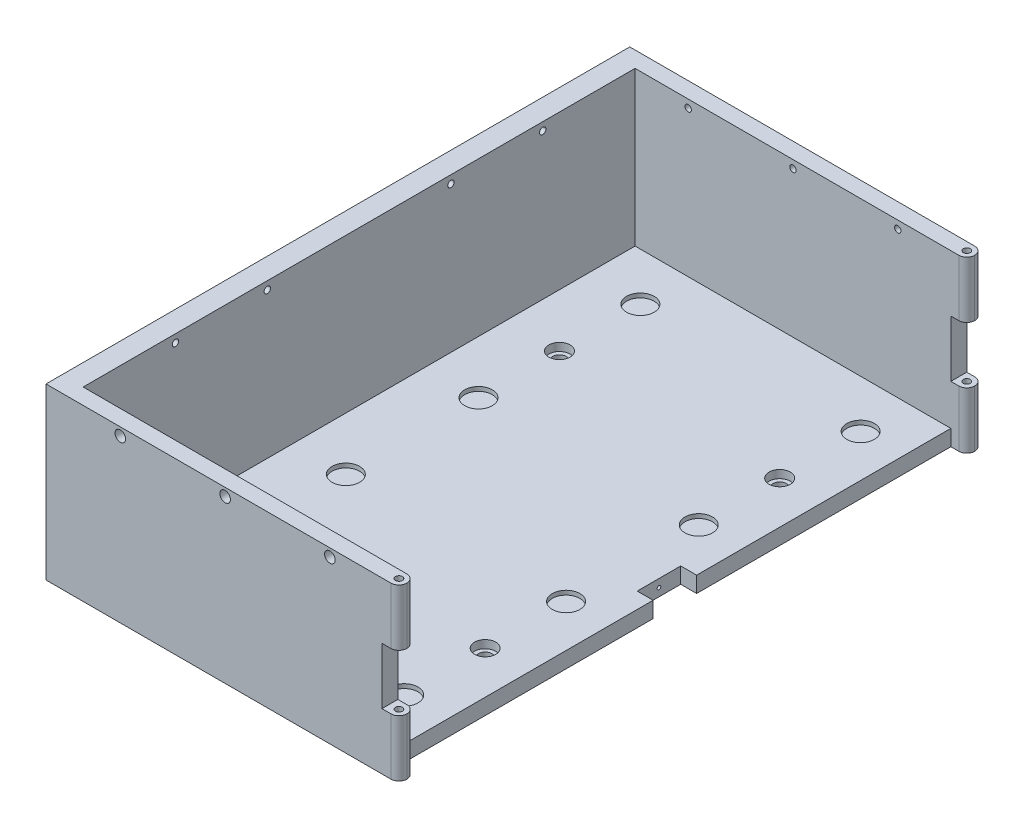
SolidWorks part; units mm, degrees
ref_plane "前视基准面" through (0, 0, 0) normal (0, 0, 1) x (1, 0, 0)
ref_plane "上视基准面" through (0, 0, 0) normal (0, 1, 0) x (1, 0, 0)
ref_plane "右视基准面" through (0, 0, 0) normal (1, 0, 0) x (0, 0, -1)
other "Configuration Table"
sketch "草图1" plane through (0, 0, 0) normal (0, 1, 0) x (1, 0, 0)
  line L1 (-28.75, -50) -> (28.75, -50)
  line L2 (-28.75, -50) -> (-28.75, 50)
  line L3 (-28.75, 50) -> (28.75, 50)
  line L4 (28.75, -50) -> (28.75, 50)
  line L5 (-28.75, -50) -> (28.75, 50) construction
  line L6 (-28.75, 50) -> (28.75, -50) construction
  point P0 (0, 0)
  dimension "D1" = 57.5
  dimension "D5" = 100
extrude "凸台-拉伸1" add sketch "草图1" along normal blind 3 contours L3 L4 L1 L2
sketch "草图2" plane through (0, 3, 0) normal (0, 1, 0) x (1, 0, 0)
  line L0 (-28.75, 50) -> (28.75, 50) construction
  line L1 (28.75, -50) -> (28.75, 50) construction
  line L2 (76.4188, 0) -> (-80.6244, 0) construction
  circle A0 centre (20.75, 43) radius 2.6
  circle A1 centre (20.75, 12.5) radius 2.6
  circle A2 centre (-20.75, 12.5) radius 2.6
  circle A3 centre (-20.75, 43) radius 2.6
  dimension "D3" = 5.2
  dimension "D1" = 30.5
  dimension "D2" = 41.5
  dimension "D4" = 7
  dimension "D5" = 8
extrude "切除-拉伸1" cut sketch "草图2" against normal blind 0.8
sketch "草图3" plane through (0, 3, 0) normal (0, 1, 0) x (1, 0, 0)
  line L0 (20.75, 43) -> (20.75, 12.5) construction
  line L1 (-20.75, 43) -> (-20.75, 12.5) construction
  circle A0 centre (20.75, 27.75) radius 1.25
  circle A1 centre (-20.75, 27.75) radius 1.25
  circle A6 centre (20.75, 27.75) radius 2
  circle A7 centre (-20.75, 27.75) radius 2
  circle A8 centre (20.75, 43) radius 2.6 construction
  circle A9 centre (20.75, 12.5) radius 2.6 construction
  circle A10 centre (-20.75, 43) radius 2.6 construction
  circle A11 centre (-20.75, 12.5) radius 2.6 construction
  dimension "D1" = 2.5
  dimension "D2" = 4
extrude "切除-拉伸2" cut sketch "草图3" against normal through all contours A0 | A1
extrude "切除-拉伸3" cut sketch "草图3<3>" against normal blind 1.5 contours A7 | A6
sketch "草图3<3>" plane through (0, 3, 0) normal (0, 1, 0) x (1, 0, 0) same geometry as "草图3"
mirror "镜向1" about plane through (0, 0, 0) normal (0, 0, 1) of "切除-拉伸3", "切除-拉伸2", "切除-拉伸1"
sketch "草图5" plane through (0, 3, 0) normal (0, 1, 0) x (1, 0, 0)
  line L0 (-28.75, -50) -> (-28.75, 50) construction
  line L1 (-28.75, -50) -> (28.75, -50)
  line L2 (-28.75, -50) -> (-28.75, -55)
  line L3 (-28.75, -55) -> (28.75, -55)
  line L4 (28.75, -50) -> (28.75, -55)
  line L5 (-28.75, -50) -> (28.75, -50) construction
  line L6 (-28.75, 50) -> (28.75, 50) construction
  line L7 (28.75, 50) -> (-28.75, 50)
  line L8 (28.75, 50) -> (28.75, 55)
  line L9 (28.75, 55) -> (-28.75, 55)
  line L10 (-28.75, 50) -> (-28.75, 55)
  line L11 (28.75, -50) -> (28.75, 50) construction
  line L12 (28.75, 52) -> (-28.75, 52)
  line L13 (28.75, -52) -> (-28.75, -52)
  line L14 (-30.75, 55) -> (-30.75, -55)
  line L15 (-28.75, 55) -> (-34.75, 55)
  line L16 (-28.75, 55) -> (-28.75, -55)
  line L17 (-28.75, -55) -> (-34.75, -55)
  line L18 (-34.75, 55) -> (-34.75, -55)
  line L19 (-28.75, 52) -> (-30.75, 52)
  line L20 (-28.75, -52) -> (-30.75, -52)
  line M13 (-28.75, 50) -> (-28.75, -50)
  dimension "D1" = 3
  dimension "D2" = 3
  dimension "D3" = 5
  dimension "D4" = 5
  dimension "D5" = 6
  dimension "D6" = 4
extrude "凸台-拉伸2" add sketch "草图5" against normal up to surface (3 mm away) contours L17 L2 L10 L15 L14 M13 | L15 L18 L17 L14 | L2 L20 L14 L17 | L19 L10 L15 L14 | L9 L10 L7 L8 | L3 L4 L1 L2 region at (-29.75, 3, 0) region at (-29.75, 3, 53.5) region at (-32.75, 3, 0) region at (-29.75, 3, -53.5) up to face at (20.75, 0, 26.5)
extrude "凸台-拉伸3" add sketch "草图5<3>" along normal blind 29 contours L4 L13 L2 L3 | L12 L8 L9 L10 | L15 L18 L17 L14 | L19 L10 L15 L14 | L2 L20 L14 L17 region at (0, 3, 53.5) region at (-29.75, 3, 53.5) region at (-32.75, 3, 0) region at (-29.75, 3, -53.5) region at (0, 3, -53.5)
sketch "草图5<3>" plane through (0, 3, 0) normal (0, 1, 0) x (1, 0, 0) same geometry as "草图5"
sketch "草图6" plane through (28.75, 0, 0) normal (1, 0, 0) x (0, 0, -1)
  line L0 (-52, 3) -> (52, 3) construction
  line L1 (-4.1, 3) -> (4.1, 3)
  line L2 (-4.1, 3) -> (-4.1, 0)
  line L3 (-4.1, 0) -> (4.1, 0)
  line L4 (4.1, 3) -> (4.1, 0)
  line L5 (-55, 0) -> (55, 0) construction
  circle A0 centre (0, 1.5) radius 0.35
  point P14 (-4.1, 1.5)
  dimension "D2" = 0.7
  dimension "D1" = 8.2
extrude "切除-拉伸4" cut sketch "草图6" against normal blind 3 contours L3 L4 L1 L2
extrude "切除-拉伸6" cut sketch "草图6<4>" against normal blind 3 from surface contours A0 starting at face at (25.75, 1.5, 0)
sketch "草图6<4>" plane through (28.75, 0, 0) normal (1, 0, 0) x (0, 0, -1) same geometry as "草图6"
sketch "草图7" plane through (28.75, 0, 0) normal (1, 0, 0) x (0, 0, -1)
  line L0 (-55, 0) -> (-55, 32) construction
  line L1 (-55, 32) -> (-52, 32)
  line L2 (-55, 32) -> (-55, 0)
  line L3 (-55, 0) -> (-52, 0)
  line L4 (-52, 32) -> (-52, 0)
  line L5 (-55, 0) -> (-4.1, 0) construction
  line L6 (55, 0) -> (55, 32) construction
  line L7 (55, 32) -> (52, 32)
  line L8 (55, 32) -> (55, 0)
  line L9 (55, 0) -> (52, 0)
  line L10 (52, 32) -> (52, 0)
  line L11 (52, 32) -> (55, 32) construction
  line L12 (4.1, 0) -> (55, 0) construction
  line L13 (-53.5, 32) -> (-53.5, 21.3333) construction
  line L14 (-55, 21.3333) -> (-52, 21.3333)
  line L15 (-55, 21.3333) -> (-55, 10.6667)
  line L16 (-55, 10.6667) -> (-52, 10.6667)
  line L17 (-52, 21.3333) -> (-52, 10.6667)
  line L18 (52, 21.3333) -> (55, 21.3333)
  line L19 (52, 21.3333) -> (52, 10.6667)
  line L20 (52, 10.6667) -> (55, 10.6667)
  line L21 (55, 21.3333) -> (55, 10.6667)
  line L22 (-53.5, 21.3333) -> (-53.5, 10.6667) construction
  line L23 (-53.5, 10.6667) -> (-53.5, 0) construction
  line M5 (-55, 0) -> (-4.1, 0)
  line M8 (-52, 3) -> (-52, 32)
  line M9 (-52, 32) -> (-55, 32)
  line M10 (-55, 32) -> (-55, 0)
extrude "凸台-拉伸4" add sketch "草图7" along normal blind 3 contours L14 L4 M10 M9 | L16 L4 M10 M5 M8 | L10 L18 L8 L7 | L20 L10 L9 L8 region at (28.75, 26.6667, 53.5) region at (28.75, 5.3333, 53.5) region at (28.75, 26.6667, -53.5) region at (28.75, 5.3333, -53.5)
fillet "圆角1" radius 1.5 8 edges at (31.75, 26.6667, -55) (31.75, 26.6667, -52) (31.75, 5.3333, -55) (31.75, 5.3333, -52) (31.75, 5.3333, 52) (31.75, 5.3333, 55) (31.75, 26.6667, 52) (31.75, 26.6667, 55)
sketch "草图8" plane through (0, 32, 0) normal (0, 1, 0) x (1, 0, 0)
  circle A0 centre (30.25, -53.5) radius 0.65
  arc A1 (30.25, -55) -> (31.75, -53.5) centre (30.25, -53.5) ccw construction
  circle A2 centre (30.25, 53.5) radius 0.65
  arc A3 (30.25, 52) -> (31.75, 53.5) centre (30.25, 53.5) ccw construction
  dimension "D1" = 1.3
extrude "切除-拉伸7" cut sketch "草图8" against normal through all
extrude "切除-拉伸8" cut sketch "草图7<3>" against normal blind 0.2 contours L2 L16 L4 L14 region at (28.75, 16, 53.5)
sketch "草图7<3>" plane through (28.75, 0, 0) normal (1, 0, 0) x (0, 0, -1) same geometry as "草图7"
sketch "草图10" plane through (0, 0, -55) normal (0, 0, -1) x (-1, 0, 0)
  circle A0 centre (-18.75, 30.5) radius 0.6
  circle A1 centre (1, 30.5) radius 0.6
  circle A2 centre (20.75, 30.5) radius 0.6
  dimension "D1" = 1.2
extrude "切除-拉伸9" cut sketch "草图10" against normal through all
sketch "草图11" plane through (-34.75, 0, 0) normal (-1, 0, 0) x (0, 0, 1)
  circle A0 centre (-34.6, 30.5) radius 0.6
  circle A1 centre (-17.3, 30.5) radius 0.6
  circle A2 centre (17.3, 30.5) radius 0.6
  circle A3 centre (34.6, 30.5) radius 0.6
  dimension "D1" = 1.2
extrude "切除-拉伸10" cut sketch "草图11" against normal through all
sketch "草图12" plane through (0, 0, -55) normal (0, 0, -1) x (-1, 0, 0)
  circle A0 centre (-18.75, 30.5) radius 1
  circle A1 centre (1, 30.5) radius 1
  circle A2 centre (20.75, 30.5) radius 1
  circle A3 centre (-18.75, 30.5) radius 0.6 construction
  circle A4 centre (1, 30.5) radius 0.6 construction
  circle A5 centre (20.75, 30.5) radius 0.6 construction
  dimension "D1" = 2
extrude "切除-拉伸11" cut sketch "草图12" against normal blind 1.5
extrude "切除-拉伸12" cut sketch "草图12<2>" along normal blind 1.5 from surface starting at face at (18.15, 30.5, 55)
sketch "草图12<2>" plane through (0, 0, -55) normal (0, 0, -1) x (-1, 0, 0) same geometry as "草图12"
sketch "草图13" plane through (-34.75, 0, 0) normal (-1, 0, 0) x (0, 0, 1)
  circle A0 centre (-34.6, 30.5) radius 1
  circle A1 centre (-17.3, 30.5) radius 1
  circle A2 centre (17.3, 30.5) radius 1
  circle A3 centre (34.6, 30.5) radius 1
  circle A5 centre (-34.6, 30.5) radius 0.6 construction
  circle A6 centre (-17.3, 30.5) radius 0.6 construction
  circle A7 centre (34.6, 30.5) radius 0.6 construction
  circle A8 centre (17.3, 30.5) radius 0.6 construction
  dimension "D1" = 2
extrude "切除-拉伸13" cut sketch "草图13" against normal blind 1.5
